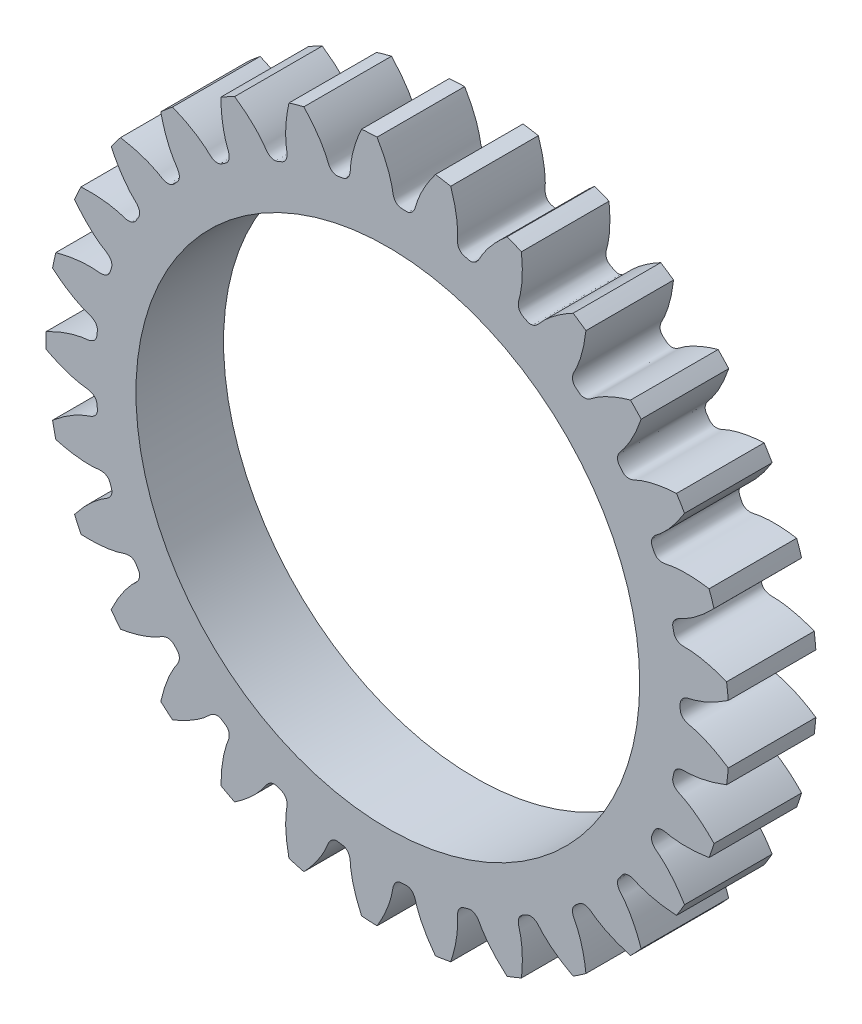
SolidWorks part; units mm, degrees
ref_plane "Front Plane" through (0, 0, 0) normal (0, 0, 1) x (1, 0, 0)
ref_plane "Top Plane" through (0, 0, 0) normal (0, 1, 0) x (1, 0, 0)
ref_plane "Right Plane" through (0, 0, 0) normal (1, 0, 0) x (0, 0, -1)
ref_axis "Axis1" through (0, 0, 55) along (0, 0, -1)
sketch "SketchRevolveSpurGear" plane through (0, 0, 0) normal (1, 0, 0) x (0, 0, -1)
  line L0 (0, 0) -> (1, 0) construction
  line L1 (-2, 0) -> (-2, 15.6)
  line L2 (-2, 15.6) -> (2, 15.6)
  line L3 (2, 15.6) -> (2, 0)
  line L4 (2, 0) -> (-2, 0)
  dimension "Side1" = 2
  dimension "OutsideRadius" = 15.6
  dimension "Side2" = 2
revolve "SpurGear" add sketch "SketchRevolveSpurGear" angle 360 about L0
sketch "SketchToothSpurGear" plane through (0, 0, 0) normal (0, 0, 1) x (1, 0, 0)
  arc A0 (15.5949, 1.3703) -> (15.5949, -1.3703) centre (0, 0) cw
  spline S0 degree 3 poles (15.5949, -1.3703) (15.4884, -1.2971) (15.3298, -1.1938) (15.1184, -1.068) (14.9699, -0.9848) (14.8276, -0.91) (14.6919, -0.8431) (14.5631, -0.7838) (14.4416, -0.7317) (14.3275, -0.6863) (14.2211, -0.6472) (14.1228, -0.614) (14.0327, -0.5861) (13.951, -0.5633) (13.8358, -0.5338) (13.7288, -0.5152) (13.6339, -0.4812) (13.5851, -0.4596) (13.5367, -0.4324) (13.4877, -0.3972) (13.4384, -0.3496) (13.3917, -0.2842) (13.3588, -0.202) (13.3461, -0.1039) (13.3521, 0) (13.3461, 0.1039) (13.3588, 0.202) (13.3917, 0.2842) (13.4384, 0.3496) (13.4877, 0.3972) (13.5367, 0.4324) (13.5851, 0.4596) (13.6339, 0.4812) (13.7288, 0.5152) (13.8358, 0.5338) (13.951, 0.5633) (14.0327, 0.5861) (14.1228, 0.614) (14.2211, 0.6472) (14.3275, 0.6863) (14.4416, 0.7317) (14.5631, 0.7838) (14.6919, 0.8431) (14.8276, 0.91) (14.9699, 0.9848) (15.1184, 1.068) (15.3298, 1.1938) (15.4884, 1.2971) (15.5949, 1.3703) knots 0 0 0 0 0.069922 0.102317 0.133002 0.161975 0.189238 0.214791 0.238632 0.260763 0.281184 0.299893 0.316892 0.332181 0.345758 0.381199 0.390682 0.400185 0.410023 0.420657 0.432723 0.446953 0.463781 0.480022 0.5 0.519978 0.536219 0.553047 0.567277 0.579343 0.589977 0.599815 0.609318 0.618801 0.654242 0.667819 0.683108 0.700107 0.718816 0.739237 0.761368 0.785209 0.810762 0.838025 0.866998 0.897683 0.930078 1 1 1 1
extrude "ToothExtrudeCutSpurGear" cut sketch "SketchToothSpurGear" against normal blind 2 and the other way blind 2
pattern_circular "PatternSpurGear" count 29 every 12.414 about axis through (0, 0, 55) along (0, 0, -1) of "ToothExtrudeCutSpurGear"
sketch "BoreRevolveSketch" plane through (0, 0, 0) normal (1, 0, 0) x (0, 0, -1)
  line L0 (0, 0) -> (1, 0) construction
  line L1 (-2, 0) -> (2, 0)
  line L2 (2, 0) -> (2, 11.5)
  line L3 (2, 11.5) -> (-2, 11.5)
  line L4 (-2, 11.5) -> (-2, 0)
  dimension "BoreSide1" = 2
  dimension "TaperSide1" = 11.5
  dimension "BoreSide2" = 2
  dimension "TaperSide2" = 11.5
revolve "BoreRevolveCut" cut sketch "BoreRevolveSketch" angle 360 about L0
sketch "AuxiliarySketchSpurGear" plane through (0, 0, 0) normal (0, 0, 1) x (1, 0, 0)
  circle A0 centre (0, 0) radius 14.5 construction
  circle A1 centre (0, 0) radius 13.6255 construction
  circle A2 centre (0, 0) radius 13.7979 construction
  circle A3 centre (0, 0) radius 15.6 construction
  circle A4 centre (0, 0) radius 13.35 construction
  dimension "PitchDiameter" = 29
  dimension "BaseDiameter" = 27.2511
  dimension "FormDiameter" = 27.5958
  dimension "MajorDiameter" = 31.2
  dimension "MinorDiameter" = 26.7
